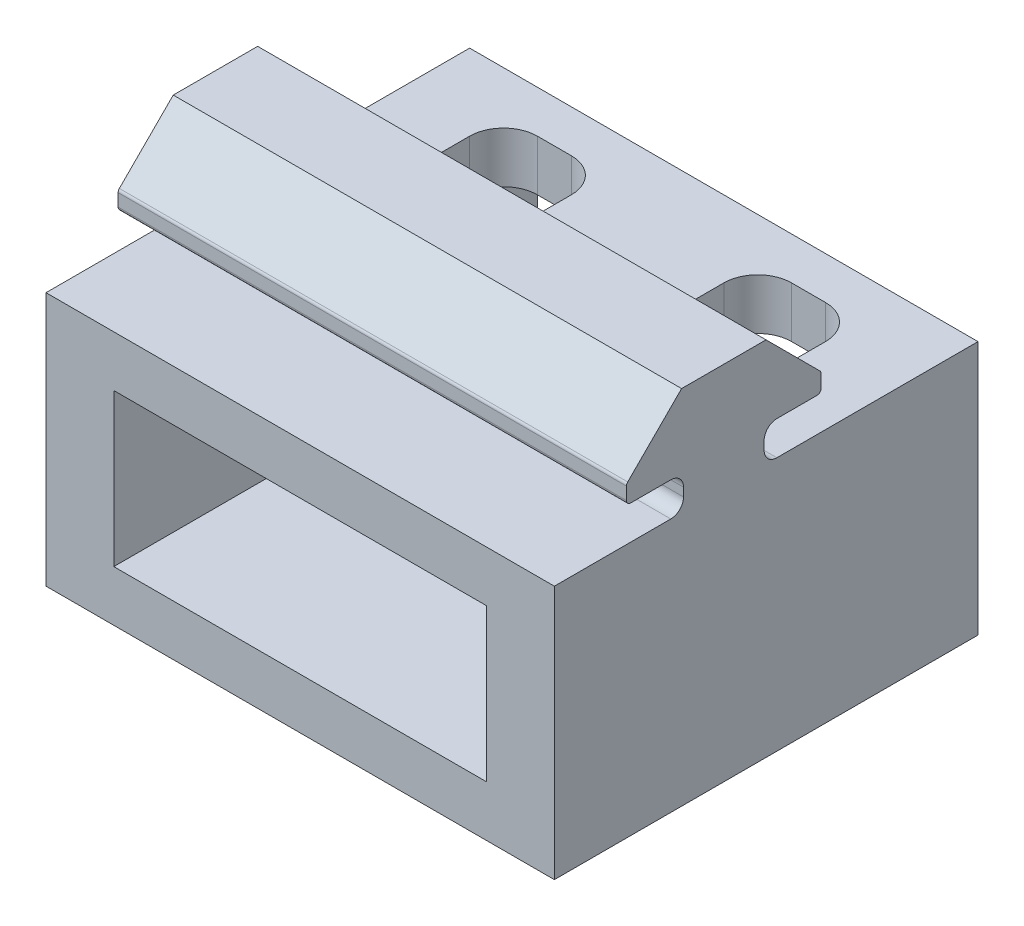
SolidWorks part; units mm, degrees
ref_plane "Front Plane" through (0, 0, 0) normal (0, 0, 1) x (1, 0, 0)
ref_plane "Top Plane" through (0, 0, 0) normal (0, 1, 0) x (1, 0, 0)
ref_plane "Right Plane" through (0, 0, 0) normal (1, 0, 0) x (0, 0, -1)
sketch "Sketch1" plane through (0, 0, 0) normal (1, 0, 0) x (0, 0, -1)
  line L255 (19.5, -26.25) -> (25, -26.25)
  line L257 (25, -26.25) -> (25, -41.25)
  line L258 (25, -41.25) -> (0, -41.25)
  line L259 (0, -41.25) -> (0, -26.25)
  line L260 (0, -26.25) -> (0.5, -26.25)
  line L266 (13.13, -26.25) -> (19.5, -26.25)
  line L267 (0.5, -26.25) -> (6.87, -26.25)
  line L268 (12.38, -25) -> (12.38, -25.5)
  line L269 (15.495, -24.25) -> (13.13, -24.25)
  line L270 (15.745, -23.2628) -> (15.745, -24)
  line L271 (12.4908, -19.905) -> (15.6718, -23.086)
  line L272 (7.5092, -19.905) -> (12.4908, -19.905)
  line L273 (4.3282, -23.086) -> (7.5092, -19.905)
  line L274 (4.255, -24) -> (4.255, -23.2628)
  line L275 (6.87, -24.25) -> (4.505, -24.25)
  line L276 (7.62, -25.5) -> (7.62, -25)
  line L277 (13.13, -26.25) -> (19.5, -26.25)
  line L278 (0.5, -26.25) -> (6.87, -26.25)
  line L279 (12.38, -25) -> (12.38, -25.5)
  line L280 (15.495, -24.25) -> (13.13, -24.25)
  line L281 (15.745, -23.2628) -> (15.745, -24)
  line L282 (12.4908, -19.905) -> (15.6718, -23.086)
  line L283 (7.5092, -19.905) -> (12.4908, -19.905)
  line L284 (4.3282, -23.086) -> (7.5092, -19.905)
  line L285 (4.255, -24) -> (4.255, -23.2628)
  line L286 (6.87, -24.25) -> (4.505, -24.25)
  line L287 (7.62, -25.5) -> (7.62, -25)
  line L294 (0, -19.13) -> (0, -25.5) construction
  arc A163 (12.38, -25.5) -> (13.13, -26.25) centre (13.13, -25.5) ccw
  arc A164 (6.87, -26.25) -> (7.62, -25.5) centre (6.87, -25.5) ccw
  arc A165 (13.13, -24.25) -> (12.38, -25) centre (13.13, -25) ccw
  arc A166 (15.495, -24.25) -> (15.745, -24) centre (15.495, -24) ccw
  arc A167 (15.745, -23.2628) -> (15.6718, -23.086) centre (15.495, -23.2628) ccw
  arc A168 (4.3282, -23.086) -> (4.255, -23.2628) centre (4.505, -23.2628) ccw
  arc A169 (4.255, -24) -> (4.505, -24.25) centre (4.505, -24) ccw
  arc A170 (7.62, -25) -> (6.87, -24.25) centre (6.87, -25) ccw
  arc A171 (12.38, -25.5) -> (13.13, -26.25) centre (13.13, -25.5) ccw
  arc A172 (6.87, -26.25) -> (7.62, -25.5) centre (6.87, -25.5) ccw
  arc A173 (13.13, -24.25) -> (12.38, -25) centre (13.13, -25) ccw
  arc A174 (15.495, -24.25) -> (15.745, -24) centre (15.495, -24) ccw
  arc A175 (15.745, -23.2628) -> (15.6718, -23.086) centre (15.495, -23.2628) ccw
  arc A176 (4.3282, -23.086) -> (4.255, -23.2628) centre (4.505, -23.2628) ccw
  arc A177 (4.255, -24) -> (4.505, -24.25) centre (4.505, -24) ccw
  arc A178 (7.62, -25) -> (6.87, -24.25) centre (6.87, -25) ccw
  dimension "D2" = 25
  dimension "D3" = 15
  dimension "D1" = 0.25
extrude "Boss-Extrude1" add sketch "Sketch1" along normal mid plane 30
sketch "Sketch2" plane through (0, 0, -25) normal (0, 0, -1) x (-1, 0, 0)
  line L15 (-15, -26.25) -> (15, -26.25) construction
  line L16 (15, -41.25) -> (15, -26.25) construction
  line L22 (11, -38.25) -> (11, -29.25)
  line L23 (-11, -38.25) -> (11, -38.25)
  line L24 (-11, -29.25) -> (-11, -38.25)
  line L25 (11, -29.25) -> (-11, -29.25)
  point P4 (0, -26.25)
  point P5 (0, -29.25)
  point P6 (15, -33.75)
  point P7 (11, -33.75)
  point P8 (11, -29.25)
  point P9 (0, 0)
  dimension "D1" = 22
  dimension "D2" = 9
extrude "Cut-Extrude1" cut sketch "Sketch2" against normal through all
sketch "Sketch3" plane through (0, 0, 0) normal (0, 1, 0) x (1, 0, 0)
  line L0 (-10.5, 20.5) -> (-10.5, 17.745)
  line L3 (10.5, 17.745) -> (10.5, 20.5)
  line L5 (15, 25) -> (15, 13.13) construction
  line L6 (15, 25) -> (-15, 25) construction
  line L7 (-4.5, 17.745) -> (-4.5, 20.5)
  line L8 (4.5, 17.745) -> (4.5, 20.5)
  line L9 (-8.5, 15.745) -> (-6.5, 15.745)
  line L10 (6.5, 15.745) -> (8.5, 15.745)
  line L11 (6.5, 22.5) -> (8.5, 22.5)
  line L12 (-8.5, 22.5) -> (-6.5, 22.5)
  line L13 (-10.5, 22.5) -> (10.5, 22.5) construction
  line L15 (15, 15.745) -> (-15, 15.745) construction
  arc A0 (8.5, 15.745) -> (10.5, 17.745) centre (8.5, 17.745) ccw
  arc A1 (-10.5, 17.745) -> (-8.5, 15.745) centre (-8.5, 17.745) ccw
  arc A2 (4.5, 17.745) -> (6.5, 15.745) centre (6.5, 17.745) ccw
  arc A3 (-4.5, 17.745) -> (-6.5, 15.745) centre (-6.5, 17.745) cw
  arc A4 (10.5, 20.5) -> (8.5, 22.5) centre (8.5, 20.5) ccw
  arc A5 (4.5, 20.5) -> (6.5, 22.5) centre (6.5, 20.5) cw
  arc A6 (-4.5, 20.5) -> (-6.5, 22.5) centre (-6.5, 20.5) ccw
  arc A7 (-10.5, 20.5) -> (-8.5, 22.5) centre (-8.5, 20.5) cw
  point P5 (10, 20)
  point P10 (0, 0)
  point P11 (0, 0)
  point P12 (0, 22.5)
  point P21 (-12.2196, 20)
  point P24 (4.2502, 20)
  point P37 (-4.5, 22.5)
  point P41 (-6, 15.8286)
  dimension "D2" = 2
  dimension "D4" = 2
  dimension "D6" = 2
  dimension "D1" = 4.5
  dimension "D3" = 6
  dimension "D5" = 2.5
extrude "Cut-Extrude2" cut sketch "Sketch3" against normal up to surface (38.25 mm away) up to face at (0, -38.25, -12.5)
sketch "Sketch4" plane through (0, -38.25, 0) normal (0, 1, 0) x (1, 0, 0)
  circle A0 centre (-7.5, 19.15) radius 1.2
  circle A1 centre (7.5, 19.15) radius 1.2
  circle A2 centre (-7.5, 19.15) radius 1.4 construction
  circle A3 centre (7.5, 19.15) radius 1.4 construction
  dimension "D1" = 2.4
extrude "Cut-Extrude3" cut sketch "Sketch4" against normal up to surface (3 mm away) up to face at (0, -41.25, -12.5)
